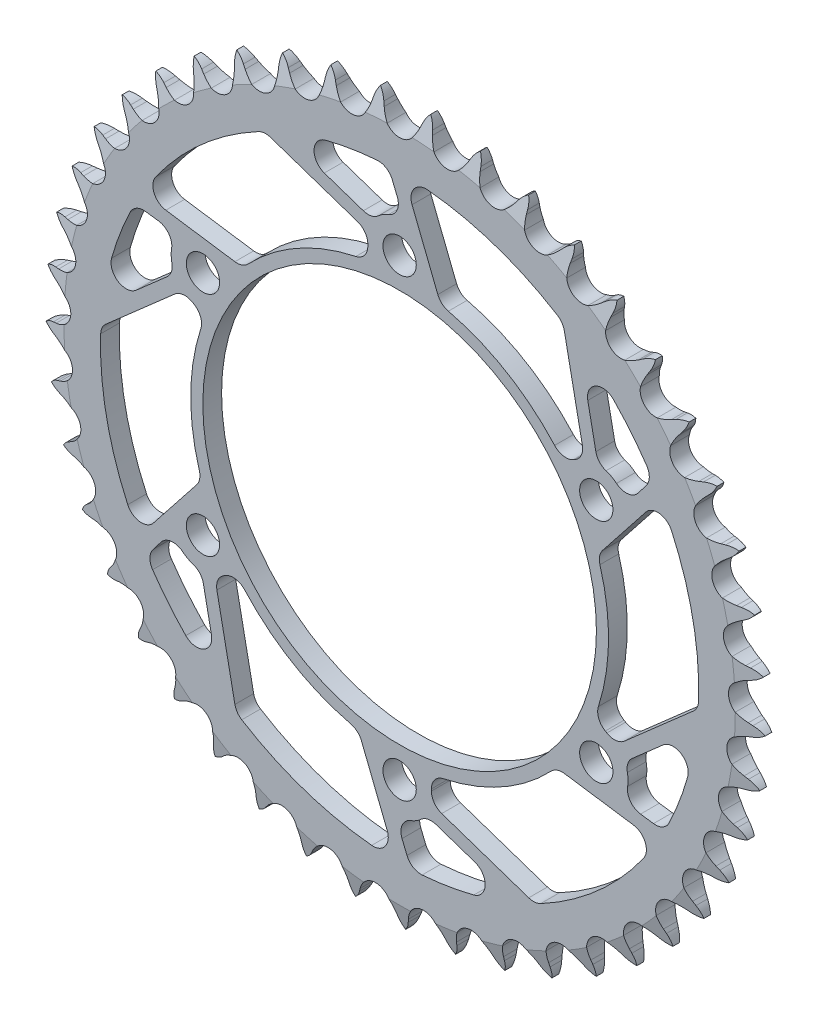
SolidWorks part; units mm, degrees
material "7075-T6, Plate (SS)"
ref_plane "Front Plane" through (0, 0, 0) normal (0, 0, 1) x (1, 0, 0)
ref_plane "Top Plane" through (0, 0, 0) normal (0, 1, 0) x (1, 0, 0)
ref_plane "Right Plane" through (0, 0, 0) normal (1, 0, 0) x (0, 0, -1)
sketch "Sketch2" plane through (0, 0, 0) normal (0, 0, 1) x (1, 0, 0)
  line L0 (0, 0) -> (0, 206.7692) construction
  line L1 (5.9565, 114.1573) -> (6.3871, 115.3681)
  line L2 (9.9891, 113.8753) -> (9.7312, 115.1342)
  line L3 (21.7861, 112.2174) -> (22.381, 113.3564)
  line L4 (25.7403, 111.3769) -> (25.6601, 112.6594)
  line L5 (37.1917, 108.0932) -> (37.9394, 109.1384)
  line L6 (-5.9565, 114.1573) -> (-6.3871, 115.3681)
  line L7 (40.9905, 106.7106) -> (41.0896, 107.9918)
  line L8 (51.8735, 101.8652) -> (52.7593, 102.7961)
  line L9 (55.4428, 99.9673) -> (55.7192, 101.2223)
  line L10 (65.5455, 93.6545) -> (66.5523, 94.4531)
  line L11 (68.816, 91.2783) -> (69.2644, 92.4826)
  line L12 (77.9418, 83.6208) -> (79.0499, 84.2716)
  line L13 (-15.8363, 112.6813) -> (-11.3291, 110.2511) construction
  line L14 (-8.2868, 118.5072) -> (3479.5369, -49759.6953) construction
  line L15 (80.8498, 80.8127) -> (81.4614, 81.9428)
  line L16 (88.8211, 71.9597) -> (90.009, 72.4498)
  line L17 (91.3099, 68.7741) -> (92.0729, 69.8081)
  line L18 (97.9715, 58.8978) -> (99.2161, 59.2179)
  line L19 (99.9928, 55.3969) -> (100.8922, 56.3147)
  line L20 (105.2151, 44.6897) -> (106.492, 44.8334)
  line L21 (106.7294, 40.9415) -> (107.7479, 41.7251)
  line L22 (110.4107, 29.6116) -> (111.6953, 29.5762)
  line L23 (111.3887, 25.6892) -> (112.5063, 26.3235)
  line L24 (113.4573, 13.9573) -> (114.7245, 13.7434)
  line L25 (113.8799, 9.9369) -> (115.0749, 10.4095)
  line L26 (114.2957, -1.9688) -> (115.5207, -2.3569)
  line L27 (114.1546, -6.0089) -> (115.4037, -5.7072)
  line L28 (112.9093, -17.8565) -> (114.0685, -18.4113)
  line L29 (112.2074, -21.8376) -> (113.4863, -21.7127)
  line L30 (109.3254, -33.3967) -> (110.396, -34.1074)
  line L31 (108.0761, -37.2414) -> (109.3601, -37.2957)
  line L32 (103.6135, -48.2868) -> (104.5748, -49.1396)
  line L33 (101.8414, -51.9202) -> (103.1052, -52.1527)
  line L34 (95.8849, -62.2371) -> (96.7182, -63.2154)
  line L35 (93.6244, -65.5885) -> (94.8436, -65.9946)
  line L36 (86.29, -74.976) -> (86.979, -76.0608)
  line L37 (83.585, -77.9802) -> (84.7359, -78.552)
  line L38 (75.0156, -86.2556) -> (75.5469, -87.4257)
  line L39 (71.9189, -88.8541) -> (72.9789, -89.5805)
  line L40 (62.2811, -95.8563) -> (62.6444, -97.089)
  line L41 (58.8528, -97.9985) -> (59.8015, -98.8654)
  line L42 (48.3344, -103.5913) -> (48.5226, -104.8625)
  line L43 (44.6413, -105.2356) -> (45.4601, -106.226)
  line L44 (33.4469, -109.31) -> (33.4563, -110.595)
  line L45 (29.5609, -110.4243) -> (30.2339, -111.5191)
  line L46 (17.9084, -112.9011) -> (17.7389, -114.175)
  line L47 (13.9052, -113.4637) -> (14.4192, -114.6415)
  line L48 (2.0213, -114.2947) -> (1.6762, -115.5326)
  line L49 (-2.0213, -114.2947) -> (-1.6762, -115.5326)
  line L50 (-13.9052, -113.4637) -> (-14.4192, -114.6415)
  line L51 (-17.9084, -112.9011) -> (-17.7389, -114.175)
  line L52 (-29.5609, -110.4243) -> (-30.2339, -111.5191)
  line L53 (-33.4469, -109.31) -> (-33.4563, -110.595)
  line L54 (-44.6413, -105.2356) -> (-45.4601, -106.226)
  line L55 (-48.3344, -103.5913) -> (-48.5226, -104.8625)
  line L56 (-58.8528, -97.9985) -> (-59.8015, -98.8654)
  line L57 (-62.2811, -95.8563) -> (-62.6444, -97.089)
  line L58 (-71.9189, -88.8541) -> (-72.9789, -89.5805)
  line L59 (-75.0156, -86.2556) -> (-75.5469, -87.4257)
  line L60 (-83.585, -77.9802) -> (-84.7359, -78.552)
  line L61 (-86.29, -74.976) -> (-86.979, -76.0608)
  line L62 (-93.6244, -65.5885) -> (-94.8436, -65.9946)
  line L63 (-95.8849, -62.2371) -> (-96.7182, -63.2154)
  line L64 (-101.8414, -51.9202) -> (-103.1052, -52.1527)
  line L65 (-103.6135, -48.2868) -> (-104.5748, -49.1396)
  line L66 (-108.0761, -37.2414) -> (-109.3601, -37.2957)
  line L67 (-109.3254, -33.3967) -> (-110.396, -34.1074)
  line L68 (-112.2074, -21.8376) -> (-113.4863, -21.7127)
  line L69 (-112.9093, -17.8565) -> (-114.0685, -18.4113)
  line L70 (-114.1546, -6.0089) -> (-115.4037, -5.7072)
  line L71 (-114.2957, -1.9688) -> (-115.5207, -2.3569)
  line L72 (-113.8799, 9.9369) -> (-115.0749, 10.4095)
  line L73 (-113.4573, 13.9573) -> (-114.7245, 13.7434)
  line L74 (-111.3887, 25.6892) -> (-112.5063, 26.3235)
  line L75 (-110.4107, 29.6116) -> (-111.6953, 29.5762)
  line L76 (-106.7294, 40.9415) -> (-107.7479, 41.7251)
  line L77 (-105.2151, 44.6897) -> (-106.492, 44.8334)
  line L78 (-99.9928, 55.3969) -> (-100.8922, 56.3147)
  line L79 (-97.9715, 58.8978) -> (-99.2161, 59.2179)
  line L80 (-91.3099, 68.7741) -> (-92.0729, 69.8081)
  line L81 (-88.8211, 71.9597) -> (-90.009, 72.4498)
  line L82 (-80.8498, 80.8127) -> (-81.4614, 81.9428)
  line L83 (-77.9418, 83.6208) -> (-79.0499, 84.2716)
  line L84 (-68.816, 91.2783) -> (-69.2644, 92.4826)
  line L85 (-65.5455, 93.6545) -> (-66.5523, 94.4531)
  line L86 (-55.4428, 99.9673) -> (-55.7192, 101.2223)
  line L87 (-51.8735, 101.8652) -> (-52.7593, 102.7961)
  line L88 (-40.9905, 106.7106) -> (-41.0896, 107.9918)
  line L89 (-37.1917, 108.0932) -> (-37.9394, 109.1384)
  line L90 (-25.7403, 111.3769) -> (-25.6601, 112.6594)
  line L91 (-21.7861, 112.2174) -> (-22.381, 113.3564)
  line L92 (-9.9891, 113.8753) -> (-9.7312, 115.1342)
  line L93 (-13.6479, 112.8344) -> (49864.5546, 3600.6581) construction
  line L94 (0, 113.7887) -> (48259.6069, -12963.3036) construction
  circle A0 centre (0, 0) radius 113.7887 construction
  arc A2 (-4.1251, 110.7548) -> (-5.9565, 114.1573) centre (6.521, 118.6791) cw
  arc A4 (-4.1251, 110.7548) -> (4.1251, 110.7548) centre (0, 113.7887) ccw
  arc A5 (-6.3871, 115.3681) -> (-8.2868, 118.5072) centre (-14.1858, 112.7928) ccw
  arc A6 (6.3871, 115.3681) -> (8.2868, 118.5072) centre (14.1858, 112.7928) cw
  arc A7 (4.1251, 110.7548) -> (5.9565, 114.1573) centre (-6.521, 118.6791) ccw
  arc A8 (9.7312, 115.1342) -> (8.2868, 118.5072) centre (1.65, 113.6694) ccw
  arc A9 (11.3291, 110.2511) -> (9.9891, 113.8753) centre (22.9745, 116.6165) cw
  arc A10 (11.3291, 110.2511) -> (19.4991, 109.1029) centre (15.8363, 112.6813) ccw
  arc A11 (19.4991, 109.1029) -> (21.7861, 112.2174) centre (10.0594, 118.4316) ccw
  arc A12 (22.381, 113.3564) -> (24.6992, 116.2006) centre (29.7455, 109.7208) cw
  arc A13 (25.6601, 112.6594) -> (24.6992, 116.2006) centre (17.4537, 112.3336) ccw
  arc A14 (26.5629, 107.6014) -> (25.7403, 111.3769) centre (38.9808, 112.2842) cw
  arc A15 (26.5629, 107.6014) -> (34.4935, 105.3273) centre (31.3644, 109.3807) ccw
  arc A16 (34.4935, 105.3273) -> (37.1917, 108.0932) centre (26.444, 115.8791) ccw
  arc A17 (37.9394, 109.1384) -> (40.6308, 111.6323) centre (44.7262, 104.5133) cw
  arc A18 (41.0896, 107.9918) -> (40.6308, 111.6323) centre (32.9176, 108.8112) ccw
  arc A19 (41.2796, 102.8574) -> (40.9905, 106.7106) centre (54.2283, 105.7664) cw
  arc A20 (41.2796, 102.8574) -> (48.8165, 99.5017) centre (46.282, 103.9512) ccw
  arc A21 (48.8165, 99.5017) -> (51.8735, 101.8652) centre (42.3139, 111.071) ccw
  arc A22 (52.7593, 102.7961) -> (55.7716, 104.8912) centre (58.8363, 97.2715) cw
  arc A23 (55.7192, 101.2223) -> (55.7716, 104.8912) centre (47.7409, 103.1711) ccw
  arc A24 (55.1928, 96.1114) -> (55.4428, 99.9673) centre (68.4204, 97.19) cw
  arc A25 (55.1928, 96.1114) -> (62.1894, 91.7395) centre (60.2988, 96.4983) ccw
  arc A26 (62.1894, 91.7395) -> (65.5455, 93.6545) centre (57.3602, 104.1012) ccw
  arc A27 (66.5523, 94.4531) -> (69.8269, 96.1085) centre (71.8013, 88.1364) cw
  arc A28 (69.2644, 92.4826) -> (69.8269, 96.1085) centre (61.6349, 95.5228) ccw
  arc A29 (68.0318, 87.4947) -> (68.816, 91.2783) centre (81.2808, 86.7218) cw
  arc A30 (68.0318, 87.4947) -> (74.3518, 82.1916) centre (73.142, 87.1672) ccw
  arc A31 (74.3518, 82.1916) -> (77.9418, 83.6208) centre (71.2901, 95.105) ccw
  arc A32 (79.0499, 84.2716) -> (82.5231, 85.4551) centre (83.3688, 77.2859) cw
  arc A33 (81.4614, 81.9428) -> (82.5231, 85.4551) centre (74.3293, 86.0152) ccw
  arc A34 (79.5466, 77.175) -> (80.8498, 80.8127) centre (92.5591, 74.5658) cw
  arc A35 (79.5466, 77.175) -> (85.0671, 71.0439) centre (84.5615, 76.1395) ccw
  arc A36 (85.0671, 71.0439) -> (88.8211, 71.9597) centre (83.8323, 84.2578) ccw
  arc A37 (90.009, 72.4498) -> (93.613, 73.1385) centre (93.3135, 64.931) cw
  arc A38 (92.0729, 69.8081) -> (93.613, 73.1385) centre (85.5769, 74.8335) ccw
  arc A39 (89.5132, 65.3532) -> (91.3099, 68.7741) centre (102.0359, 60.9583) cw
  arc A40 (89.5132, 65.3532) -> (94.1266, 58.5135) centre (94.3351, 63.6298) ccw
  arc A41 (94.1266, 58.5135) -> (97.9715, 58.8978) centre (94.7429, 71.7706) ccw
  arc A42 (99.2161, 59.2179) -> (102.8809, 59.3983) centre (101.4421, 51.3124) cw
  arc A43 (100.8922, 56.3147) -> (102.8809, 59.3983) centre (95.1589, 62.1952) ccw
  arc A44 (97.7375, 52.2593) -> (99.9928, 55.3969) centre (109.5266, 46.1645) cw
  arc A45 (97.7375, 52.2593) -> (101.3541, 44.8441) centre (102.2726, 49.8817) ccw
  arc A46 (101.3541, 44.8441) -> (105.2151, 44.6897) centre (103.8094, 57.8865) ccw
  arc A47 (106.492, 44.8334) -> (110.1463, 44.502) centre (107.5962, 36.695) cw
  arc A48 (107.7479, 41.7251) -> (110.1463, 44.502) centre (102.8887, 48.3464) ccw
  arc A49 (104.0594, 38.1483) -> (106.7294, 40.9415) centre (114.8856, 30.472) cw
  arc A50 (104.0594, 38.1483) -> (106.6088, 30.3019) centre (108.2195, 35.1626) ccw
  arc A51 (106.6088, 30.3019) -> (110.4107, 29.6116) centre (110.8554, 42.8757) ccw
  arc A52 (111.6953, 29.5762) -> (115.2678, 28.7395) centre (111.656, 21.3634) cw
  arc A53 (112.5063, 26.3235) -> (115.2678, 28.7395) centre (108.6159, 33.5565) ccw
  arc A54 (108.3559, 23.2948) -> (111.3887, 25.6892) centre (118.0084, 14.1865) cw
  arc A55 (108.3559, 23.2948) -> (109.7885, 15.1699) centre (112.06, 19.7592) ccw
  arc A56 (109.7885, 15.1699) -> (113.4573, 13.9573) centre (115.7437, 27.0303) ccw
  arc A57 (114.7245, 13.7434) -> (118.1458, 12.4176) centre (113.5426, 5.616) cw
  arc A58 (115.0749, 10.4095) -> (118.1458, 12.4176) centre (112.229, 18.1136) ccw
  arc A59 (110.5434, 7.9879) -> (113.8799, 9.9369) centre (118.8343, -2.3752) cw
  arc A60 (110.5434, 7.9879) -> (110.8313, -0.2573) centre (113.7194, 3.9712) ccw
  arc A61 (110.8313, -0.2573) -> (114.2957, -1.9688) centre (118.3792, 10.6589) ccw
  arc A62 (115.5207, -2.3569) -> (118.7242, -4.1459) centre (113.2192, -10.2407) cw
  arc A63 (115.4037, -5.7072) -> (118.7242, -4.1459) centre (113.6577, 2.318) ccw
  arc A64 (110.5793, -7.4745) -> (114.1546, -6.0089) centre (117.3473, -18.8906) cw
  arc A65 (110.5793, -7.4745) -> (109.7169, -15.6795) centre (113.1654, -11.8942) ccw
  arc A66 (109.7169, -15.6795) -> (112.9093, -17.8565) centre (118.7106, -5.9201) ccw
  arc A67 (114.0685, -18.4113) -> (116.9918, -20.6288) centre (110.6921, -25.8981) cw
  arc A68 (113.4863, -21.7127) -> (116.9918, -20.6288) centre (112.8742, -13.5226) ccw
  arc A69 (108.4629, -22.7914) -> (112.2074, -21.8376) centre (113.5762, -35.0384) cw
  arc A70 (108.4629, -22.7914) -> (106.467, -30.7966) centre (110.4087, -27.528) ccw
  arc A71 (106.467, -30.7966) -> (109.3254, -33.3967) centre (116.7314, -22.3838) ccw
  arc A72 (110.396, -34.1074) -> (112.9823, -36.7102) centre (106.0105, -41.0515) cw
  arc A73 (109.3601, -37.2957) -> (112.9823, -36.7102) centre (109.8938, -29.1001) ccw
  arc A74 (104.2354, -37.6648) -> (108.0761, -37.2414) centre (107.5945, -50.5041) cw
  arc A75 (104.2354, -37.6648) -> (101.1448, -45.3142) centre (105.5031, -42.626) ccw
  arc A76 (101.1448, -45.3142) -> (103.6135, -48.2868) centre (112.4801, -38.4118) ccw
  arc A77 (104.5748, -49.1396) -> (106.7737, -52.077) centre (99.2656, -55.4058) cw
  arc A78 (103.1052, -52.1527) -> (106.7737, -52.077) centre (104.7743, -44.1112) ccw
  arc A79 (97.979, -51.805) -> (101.8414, -51.9202) centre (99.5186, -64.9869) cw
  arc A80 (97.979, -51.805) -> (93.8539, -58.9499) centre (98.5439, -56.8944) ccw
  arc A81 (93.8539, -58.9499) -> (95.8849, -62.2371) centre (106.0396, -53.6922) ccw
  arc A82 (96.7182, -63.2154) -> (98.4869, -66.4302) centre (90.5886, -68.6817) cw
  arc A83 (94.8436, -65.9946) -> (98.4869, -66.4302) centre (97.6156, -58.2636) ccw
  arc A84 (89.8157, -64.9369) -> (93.6244, -65.5885) centre (89.5057, -78.2047) cw
  arc A85 (89.8157, -64.9369) -> (84.7363, -71.4381) centre (89.6667, -70.0553) ccw
  arc A86 (84.7363, -71.4381) -> (86.29, -74.976) centre (97.5351, -67.9275) ccw
  arc A87 (86.979, -76.0608) -> (88.2831, -79.4905) centre (80.1483, -80.6207) cw
  arc A88 (84.7359, -78.552) -> (88.2831, -79.4905) centre (88.5569, -71.2821) ccw
  arc A89 (79.9041, -76.8048) -> (83.585, -77.9802) centre (77.7506, -89.9004) cw
  arc A90 (79.9041, -76.8048) -> (73.9694, -82.5359) centre (79.0443, -81.8528) ccw
  arc A91 (73.9694, -82.5359) -> (75.0156, -86.2556) centre (87.1322, -80.8407) ccw
  arc A92 (75.5469, -87.4257) -> (76.361, -91.0035) centre (68.1481, -90.9906) cw
  arc A93 (72.9789, -89.5805) -> (76.361, -91.0035) centre (77.7745, -82.9131) ccw
  arc A94 (68.4373, -87.1779) -> (71.9189, -88.8541) centre (64.4822, -99.8463) cw
  arc A95 (68.4373, -87.1779) -> (61.7628, -92.0272) centre (66.8833, -92.057) ccw
  arc A96 (61.7628, -92.0272) -> (62.2811, -95.8563) centre (75.0334, -92.1804) ccw
  arc A97 (62.6444, -97.089) -> (62.9526, -100.7452) centre (54.8214, -99.5895) cw
  arc A98 (59.8015, -98.8654) -> (62.9526, -100.7452) centre (65.4783, -92.9303) ccw
  arc A99 (55.6385, -95.8541) -> (58.8528, -97.9985) centre (49.9588, -107.8488) cw
  arc A100 (55.6385, -95.8541) -> (48.354, -99.7273) centre (53.4206, -100.4695) ccw
  arc A101 (48.354, -99.7273) -> (48.3344, -103.5913) centre (61.4741, -101.726) ccw
  arc A102 (48.5226, -104.8625) -> (48.3189, -108.5261) centre (40.4277, -106.25) cw
  arc A103 (45.4601, -106.226) -> (48.3189, -108.5261) centre (51.9077, -101.1388) ccw
  arc A104 (41.7567, -102.6646) -> (44.6413, -105.2356) centre (34.4629, -113.7522) cw
  arc A105 (41.7567, -102.6646) -> (34.0041, -105.4864) centre (38.918, -106.9264) ccw
  arc A106 (34.0041, -105.4864) -> (33.4469, -109.31) centre (46.7184, -109.2915) ccw
  arc A107 (33.4563, -110.595) -> (32.7448, -114.1946) centre (25.2471, -110.8424) cw
  arc A108 (30.2339, -111.5191) -> (32.7448, -114.1946) centre (37.3267, -107.3786) ccw
  arc A109 (27.0622, -107.4769) -> (29.5609, -110.4243) centre (18.2963, -117.4414) cw
  arc A110 (27.0622, -107.4769) -> (18.9923, -109.1922) centre (23.658, -111.3022) ccw
  arc A111 (18.9923, -109.1922) -> (17.9084, -112.9011) centre (31.0533, -114.7299) ccw
  arc A112 (17.7389, -114.175) -> (16.5333, -117.6405) centre (9.5752, -113.2774) cw
  arc A113 (14.4192, -114.6415) -> (16.5333, -117.6405) centre (22.0193, -111.5285) ccw
  arc A114 (11.8409, -110.1973) -> (13.9052, -113.4637) centre (1.7735, -118.8448) cw
  arc A115 (11.8409, -110.1973) -> (3.6108, -110.7728) centre (7.9375, -113.5115) ccw
  arc A116 (3.6108, -110.7728) -> (2.0213, -114.2947) centre (14.7837, -117.9351) ccw
  arc A117 (1.6762, -115.5326) -> (0, -118.7966) centre (-6.2832, -113.5076) cw
  arc A118 (-1.6762, -115.5326) -> (0, -118.7966) centre (6.2832, -113.5076) ccw
  arc A119 (-3.6108, -110.7728) -> (-2.0213, -114.2947) centre (-14.7837, -117.9351) cw
  arc A120 (-3.6108, -110.7728) -> (-11.8409, -110.1973) centre (-7.9375, -113.5115) ccw
  arc A121 (-11.8409, -110.1973) -> (-13.9052, -113.4637) centre (-1.7735, -118.8448) ccw
  arc A122 (-14.4192, -114.6415) -> (-16.5333, -117.6405) centre (-22.0193, -111.5285) cw
  arc A123 (-17.7389, -114.175) -> (-16.5333, -117.6405) centre (-9.5752, -113.2774) ccw
  arc A124 (-18.9923, -109.1922) -> (-17.9084, -112.9011) centre (-31.0533, -114.7299) cw
  arc A125 (-18.9923, -109.1922) -> (-27.0622, -107.4769) centre (-23.658, -111.3022) ccw
  arc A126 (-27.0622, -107.4769) -> (-29.5609, -110.4243) centre (-18.2963, -117.4414) ccw
  arc A127 (-30.2339, -111.5191) -> (-32.7448, -114.1946) centre (-37.3267, -107.3786) cw
  arc A128 (-33.4563, -110.595) -> (-32.7448, -114.1946) centre (-25.2471, -110.8424) ccw
  arc A129 (-34.0041, -105.4864) -> (-33.4469, -109.31) centre (-46.7184, -109.2915) cw
  arc A130 (-34.0041, -105.4864) -> (-41.7567, -102.6646) centre (-38.918, -106.9264) ccw
  arc A131 (-41.7567, -102.6646) -> (-44.6413, -105.2356) centre (-34.4629, -113.7522) ccw
  arc A132 (-45.4601, -106.226) -> (-48.3189, -108.5261) centre (-51.9077, -101.1388) cw
  arc A133 (-48.5226, -104.8625) -> (-48.3189, -108.5261) centre (-40.4277, -106.25) ccw
  arc A134 (-48.354, -99.7273) -> (-48.3344, -103.5913) centre (-61.4741, -101.726) cw
  arc A135 (-48.354, -99.7273) -> (-55.6385, -95.8541) centre (-53.4206, -100.4695) ccw
  arc A136 (-55.6385, -95.8541) -> (-58.8528, -97.9985) centre (-49.9588, -107.8488) ccw
  arc A137 (-59.8015, -98.8654) -> (-62.9526, -100.7452) centre (-65.4783, -92.9303) cw
  arc A138 (-62.6444, -97.089) -> (-62.9526, -100.7452) centre (-54.8214, -99.5895) ccw
  arc A139 (-61.7628, -92.0272) -> (-62.2811, -95.8563) centre (-75.0334, -92.1804) cw
  arc A140 (-61.7628, -92.0272) -> (-68.4373, -87.1779) centre (-66.8833, -92.057) ccw
  arc A141 (-68.4373, -87.1779) -> (-71.9189, -88.8541) centre (-64.4822, -99.8463) ccw
  arc A142 (-72.9789, -89.5805) -> (-76.361, -91.0035) centre (-77.7745, -82.9131) cw
  arc A143 (-75.5469, -87.4257) -> (-76.361, -91.0035) centre (-68.1481, -90.9906) ccw
  arc A144 (-73.9694, -82.5359) -> (-75.0156, -86.2556) centre (-87.1322, -80.8407) cw
  arc A145 (-73.9694, -82.5359) -> (-79.9041, -76.8048) centre (-79.0443, -81.8528) ccw
  arc A146 (-79.9041, -76.8048) -> (-83.585, -77.9802) centre (-77.7506, -89.9004) ccw
  arc A147 (-84.7359, -78.552) -> (-88.2831, -79.4905) centre (-88.5569, -71.2821) cw
  arc A148 (-86.979, -76.0608) -> (-88.2831, -79.4905) centre (-80.1483, -80.6207) ccw
  arc A149 (-84.7363, -71.4381) -> (-86.29, -74.976) centre (-97.5351, -67.9275) cw
  arc A150 (-84.7363, -71.4381) -> (-89.8157, -64.9369) centre (-89.6667, -70.0553) ccw
  arc A151 (-89.8157, -64.9369) -> (-93.6244, -65.5885) centre (-89.5057, -78.2047) ccw
  arc A152 (-94.8436, -65.9946) -> (-98.4869, -66.4302) centre (-97.6156, -58.2636) cw
  arc A153 (-96.7182, -63.2154) -> (-98.4869, -66.4302) centre (-90.5886, -68.6817) ccw
  arc A154 (-93.8539, -58.9499) -> (-95.8849, -62.2371) centre (-106.0396, -53.6922) cw
  arc A155 (-93.8539, -58.9499) -> (-97.979, -51.805) centre (-98.5439, -56.8944) ccw
  arc A156 (-97.979, -51.805) -> (-101.8414, -51.9202) centre (-99.5186, -64.9869) ccw
  arc A157 (-103.1052, -52.1527) -> (-106.7737, -52.077) centre (-104.7743, -44.1112) cw
  arc A158 (-104.5748, -49.1396) -> (-106.7737, -52.077) centre (-99.2656, -55.4058) ccw
  arc A159 (-101.1448, -45.3142) -> (-103.6135, -48.2868) centre (-112.4801, -38.4118) cw
  arc A160 (-101.1448, -45.3142) -> (-104.2354, -37.6648) centre (-105.5031, -42.626) ccw
  arc A161 (-104.2354, -37.6648) -> (-108.0761, -37.2414) centre (-107.5945, -50.5041) ccw
  arc A162 (-109.3601, -37.2957) -> (-112.9823, -36.7102) centre (-109.8938, -29.1001) cw
  arc A163 (-110.396, -34.1074) -> (-112.9823, -36.7102) centre (-106.0105, -41.0515) ccw
  arc A164 (-106.467, -30.7966) -> (-109.3254, -33.3967) centre (-116.7314, -22.3838) cw
  arc A165 (-106.467, -30.7966) -> (-108.4629, -22.7914) centre (-110.4087, -27.528) ccw
  arc A166 (-108.4629, -22.7914) -> (-112.2074, -21.8376) centre (-113.5762, -35.0384) ccw
  arc A167 (-113.4863, -21.7127) -> (-116.9918, -20.6288) centre (-112.8742, -13.5226) cw
  arc A168 (-114.0685, -18.4113) -> (-116.9918, -20.6288) centre (-110.6921, -25.8981) ccw
  arc A169 (-109.7169, -15.6795) -> (-112.9093, -17.8565) centre (-118.7106, -5.9201) cw
  arc A170 (-109.7169, -15.6795) -> (-110.5793, -7.4745) centre (-113.1654, -11.8942) ccw
  arc A171 (-110.5793, -7.4745) -> (-114.1546, -6.0089) centre (-117.3473, -18.8906) ccw
  arc A172 (-115.4037, -5.7072) -> (-118.7242, -4.1459) centre (-113.6577, 2.318) cw
  arc A173 (-115.5207, -2.3569) -> (-118.7242, -4.1459) centre (-113.2192, -10.2407) ccw
  arc A174 (-110.8313, -0.2573) -> (-114.2957, -1.9688) centre (-118.3792, 10.6589) cw
  arc A175 (-110.8313, -0.2573) -> (-110.5434, 7.9879) centre (-113.7194, 3.9712) ccw
  arc A176 (-110.5434, 7.9879) -> (-113.8799, 9.9369) centre (-118.8343, -2.3752) ccw
  arc A177 (-115.0749, 10.4095) -> (-118.1458, 12.4176) centre (-112.229, 18.1136) cw
  arc A178 (-114.7245, 13.7434) -> (-118.1458, 12.4176) centre (-113.5426, 5.616) ccw
  arc A179 (-109.7885, 15.1699) -> (-113.4573, 13.9573) centre (-115.7437, 27.0303) cw
  arc A180 (-109.7885, 15.1699) -> (-108.3559, 23.2948) centre (-112.06, 19.7592) ccw
  arc A181 (-108.3559, 23.2948) -> (-111.3887, 25.6892) centre (-118.0084, 14.1865) ccw
  arc A182 (-112.5063, 26.3235) -> (-115.2678, 28.7395) centre (-108.6159, 33.5565) cw
  arc A183 (-111.6953, 29.5762) -> (-115.2678, 28.7395) centre (-111.656, 21.3634) ccw
  arc A184 (-106.6088, 30.3019) -> (-110.4107, 29.6116) centre (-110.8554, 42.8757) cw
  arc A185 (-106.6088, 30.3019) -> (-104.0594, 38.1483) centre (-108.2195, 35.1626) ccw
  arc A186 (-104.0594, 38.1483) -> (-106.7294, 40.9415) centre (-114.8856, 30.472) ccw
  arc A187 (-107.7479, 41.7251) -> (-110.1463, 44.502) centre (-102.8887, 48.3464) cw
  arc A188 (-106.492, 44.8334) -> (-110.1463, 44.502) centre (-107.5962, 36.695) ccw
  arc A189 (-101.3541, 44.8441) -> (-105.2151, 44.6897) centre (-103.8094, 57.8865) cw
  arc A190 (-101.3541, 44.8441) -> (-97.7375, 52.2593) centre (-102.2726, 49.8817) ccw
  arc A191 (-97.7375, 52.2593) -> (-99.9928, 55.3969) centre (-109.5266, 46.1645) ccw
  arc A192 (-100.8922, 56.3147) -> (-102.8809, 59.3983) centre (-95.1589, 62.1952) cw
  arc A193 (-99.2161, 59.2179) -> (-102.8809, 59.3983) centre (-101.4421, 51.3124) ccw
  arc A194 (-94.1266, 58.5135) -> (-97.9715, 58.8978) centre (-94.7429, 71.7706) cw
  arc A195 (-94.1266, 58.5135) -> (-89.5132, 65.3532) centre (-94.3351, 63.6298) ccw
  arc A196 (-89.5132, 65.3532) -> (-91.3099, 68.7741) centre (-102.0359, 60.9583) ccw
  arc A197 (-92.0729, 69.8081) -> (-93.613, 73.1385) centre (-85.5769, 74.8335) cw
  arc A198 (-90.009, 72.4498) -> (-93.613, 73.1385) centre (-93.3135, 64.931) ccw
  arc A199 (-85.0671, 71.0439) -> (-88.8211, 71.9597) centre (-83.8323, 84.2578) cw
  arc A200 (-85.0671, 71.0439) -> (-79.5466, 77.175) centre (-84.5615, 76.1395) ccw
  arc A201 (-79.5466, 77.175) -> (-80.8498, 80.8127) centre (-92.5591, 74.5658) ccw
  arc A202 (-81.4614, 81.9428) -> (-82.5231, 85.4551) centre (-74.3293, 86.0152) cw
  arc A203 (-79.0499, 84.2716) -> (-82.5231, 85.4551) centre (-83.3688, 77.2859) ccw
  arc A204 (-74.3518, 82.1916) -> (-77.9418, 83.6208) centre (-71.2901, 95.105) cw
  arc A205 (-74.3518, 82.1916) -> (-68.0318, 87.4947) centre (-73.142, 87.1672) ccw
  arc A206 (-68.0318, 87.4947) -> (-68.816, 91.2783) centre (-81.2808, 86.7218) ccw
  arc A207 (-69.2644, 92.4826) -> (-69.8269, 96.1085) centre (-61.6349, 95.5228) cw
  arc A208 (-66.5523, 94.4531) -> (-69.8269, 96.1085) centre (-71.8013, 88.1364) ccw
  arc A209 (-62.1894, 91.7395) -> (-65.5455, 93.6545) centre (-57.3602, 104.1012) cw
  arc A210 (-62.1894, 91.7395) -> (-55.1928, 96.1114) centre (-60.2988, 96.4983) ccw
  arc A211 (-55.1928, 96.1114) -> (-55.4428, 99.9673) centre (-68.4204, 97.19) ccw
  arc A212 (-55.7192, 101.2223) -> (-55.7716, 104.8912) centre (-47.7409, 103.1711) cw
  arc A213 (-52.7593, 102.7961) -> (-55.7716, 104.8912) centre (-58.8363, 97.2715) ccw
  arc A214 (-48.8165, 99.5017) -> (-51.8735, 101.8652) centre (-42.3139, 111.071) cw
  arc A215 (-48.8165, 99.5017) -> (-41.2796, 102.8574) centre (-46.282, 103.9512) ccw
  arc A216 (-41.2796, 102.8574) -> (-40.9905, 106.7106) centre (-54.2283, 105.7664) ccw
  arc A217 (-41.0896, 107.9918) -> (-40.6308, 111.6323) centre (-32.9176, 108.8112) cw
  arc A218 (-37.9394, 109.1384) -> (-40.6308, 111.6323) centre (-44.7262, 104.5133) ccw
  arc A219 (-34.4935, 105.3273) -> (-37.1917, 108.0932) centre (-26.444, 115.8791) cw
  arc A220 (-34.4935, 105.3273) -> (-26.5629, 107.6014) centre (-31.3644, 109.3807) ccw
  arc A221 (-26.5629, 107.6014) -> (-25.7403, 111.3769) centre (-38.9808, 112.2842) ccw
  arc A222 (-25.6601, 112.6594) -> (-24.6992, 116.2006) centre (-17.4537, 112.3336) cw
  arc A223 (-22.381, 113.3564) -> (-24.6992, 116.2006) centre (-29.7455, 109.7208) ccw
  arc A224 (-19.4991, 109.1029) -> (-21.7861, 112.2174) centre (-10.0594, 118.4316) cw
  arc A225 (-19.4991, 109.1029) -> (-11.3291, 110.2511) centre (-15.8363, 112.6813) ccw
  arc A226 (-11.3291, 110.2511) -> (-9.9891, 113.8753) centre (-22.9745, 116.6165) ccw
  arc A227 (-9.7312, 115.1342) -> (-8.2868, 118.5072) centre (-1.65, 113.6694) cw
  point P5 (4.1251, 110.7548)
  point P7 (0, 113.7887)
  point P9 (6.5478, 118.6044)
  point P12 (0, 118.6044)
  point P15 (6.5478, 113.7887)
  point P19 (6.3871, 115.3681)
  point P20 (8.2868, 118.5072)
  point P24 (-14.1894, 113.7887)
  point P25 (-14.1858, 112.7928)
  point P27 (19.4991, 109.1029)
  point P29 (0, 112.7965)
  point P30 (-8.2868, 118.5072)
  point P35 (-6.3871, 115.3681)
  point P43 (8.2868, 118.5072)
  point P45 (9.7312, 115.1342)
  point P49 (34.4935, 105.3273)
  point P59 (24.6992, 116.2006)
  point P61 (25.6601, 112.6594)
  point P65 (48.8165, 99.5017)
  point P75 (40.6308, 111.6323)
  point P77 (41.0896, 107.9918)
  point P81 (62.1894, 91.7395)
  point P91 (55.7716, 104.8912)
  point P93 (55.7192, 101.2223)
  point P97 (74.3518, 82.1916)
  point P107 (69.8269, 96.1085)
  point P109 (69.2644, 92.4826)
  point P113 (85.0671, 71.0439)
  point P123 (82.5231, 85.4551)
  point P125 (81.4614, 81.9428)
  point P126 (5.1653, 112.3891)
  point P129 (94.1266, 58.5135)
  point P139 (93.613, 73.1385)
  point P141 (92.0729, 69.8081)
  point P145 (101.3541, 44.8441)
  point P155 (102.8809, 59.3983)
  point P157 (100.8922, 56.3147)
  point P161 (106.6088, 30.3019)
  point P171 (110.1463, 44.502)
  point P173 (107.7479, 41.7251)
  point P177 (109.7885, 15.1699)
  point P187 (115.2678, 28.7395)
  point P189 (112.5063, 26.3235)
  point P193 (110.8313, -0.2573)
  point P203 (118.1458, 12.4176)
  point P205 (115.0749, 10.4095)
  point P209 (109.7169, -15.6795)
  point P219 (118.7242, -4.1459)
  point P221 (115.4037, -5.7072)
  point P225 (106.467, -30.7966)
  point P235 (116.9918, -20.6288)
  point P237 (113.4863, -21.7127)
  point P241 (101.1448, -45.3142)
  point P251 (112.9823, -36.7102)
  point P253 (109.3601, -37.2957)
  point P257 (93.8539, -58.9499)
  point P267 (106.7737, -52.077)
  point P269 (103.1052, -52.1527)
  point P273 (84.7363, -71.4381)
  point P283 (98.4869, -66.4302)
  point P285 (94.8436, -65.9946)
  point P289 (73.9694, -82.5359)
  point P299 (88.2831, -79.4904)
  point P301 (84.7359, -78.552)
  point P305 (61.7628, -92.0272)
  point P315 (76.361, -91.0035)
  point P317 (72.9789, -89.5805)
  point P321 (48.354, -99.7273)
  point P331 (62.9526, -100.7452)
  point P333 (59.8015, -98.8654)
  point P337 (34.0041, -105.4864)
  point P347 (48.3189, -108.5261)
  point P349 (45.4601, -106.226)
  point P353 (18.9923, -109.1922)
  point P363 (32.7448, -114.1946)
  point P365 (30.2339, -111.5191)
  point P369 (3.6108, -110.7728)
  point P379 (16.5333, -117.6405)
  point P381 (14.4192, -114.6415)
  point P385 (-11.8409, -110.1973)
  point P395 (0, -118.7966)
  point P397 (-1.6762, -115.5326)
  point P401 (-27.0622, -107.4769)
  point P411 (-16.5333, -117.6405)
  point P413 (-17.7389, -114.175)
  point P417 (-41.7567, -102.6646)
  point P427 (-32.7448, -114.1946)
  point P429 (-33.4563, -110.595)
  point P433 (-55.6385, -95.8541)
  point P443 (-48.3189, -108.5261)
  point P445 (-48.5226, -104.8625)
  point P449 (-68.4373, -87.1779)
  point P459 (-62.9526, -100.7452)
  point P461 (-62.6444, -97.089)
  point P465 (-79.9041, -76.8048)
  point P475 (-76.361, -91.0035)
  point P477 (-75.5469, -87.4257)
  point P481 (-89.8157, -64.9369)
  point P491 (-88.2831, -79.4904)
  point P493 (-86.979, -76.0608)
  point P497 (-97.979, -51.805)
  point P507 (-98.4869, -66.4302)
  point P509 (-96.7182, -63.2154)
  point P513 (-104.2354, -37.6648)
  point P523 (-106.7737, -52.077)
  point P525 (-104.5748, -49.1396)
  point P529 (-108.4629, -22.7914)
  point P539 (-112.9823, -36.7102)
  point P541 (-110.396, -34.1074)
  point P545 (-110.5793, -7.4745)
  point P555 (-116.9918, -20.6288)
  point P557 (-114.0685, -18.4113)
  point P561 (-110.5434, 7.9879)
  point P571 (-118.7242, -4.1459)
  point P573 (-115.5207, -2.3569)
  point P577 (-108.3559, 23.2948)
  point P587 (-118.1458, 12.4176)
  point P589 (-114.7245, 13.7434)
  point P593 (-104.0594, 38.1483)
  point P603 (-115.2678, 28.7395)
  point P605 (-111.6953, 29.5762)
  point P609 (-97.7375, 52.2593)
  point P619 (-110.1463, 44.502)
  point P621 (-106.492, 44.8334)
  point P625 (-89.5132, 65.3532)
  point P635 (-102.8809, 59.3983)
  point P637 (-99.2161, 59.2179)
  point P641 (-79.5466, 77.175)
  point P651 (-93.613, 73.1385)
  point P653 (-90.009, 72.4498)
  point P657 (-68.0318, 87.4947)
  point P667 (-82.5231, 85.4551)
  point P669 (-79.0499, 84.2716)
  point P673 (-55.1928, 96.1114)
  point P683 (-69.8269, 96.1085)
  point P685 (-66.5523, 94.4531)
  point P689 (-41.2796, 102.8574)
  point P699 (-55.7716, 104.8912)
  point P701 (-52.7593, 102.7961)
  point P705 (-26.5629, 107.6014)
  point P715 (-40.6308, 111.6323)
  point P717 (-37.9394, 109.1384)
  point P721 (-11.3291, 110.2511)
  point P731 (-24.6992, 116.2006)
  point P733 (-22.381, 113.3564)
  point P736 (0, 0)
  dimension "D1" = 227.5774
  dimension "D11" = 13.2715
  dimension "D2" = 45
extrude "Boss-Extrude2" add sketch "Sketch2" along normal blind 6.1976
ref_axis "Axis1" through (0, 0, -0.3099) along (0, 0, 1)
ref_plane "Plane1" through (0, 0, 3.0988) normal (0, 0, -1) x (-1, 0, 0)
ref_plane "Plane2" through (0, 0, 0) normal (-0.9781, -0.2079, 0) x (0, 0, 1)
sketch "Sketch4" plane through (0, 0, 0) normal (0.9781, 0.2079, 0) x (0, 0, -1)
  line L0 (-6.1976, 110.8591) -> (-4.2132, 118.7966)
  line L1 (-6.1976, 118.7966) -> (0, 118.7966) construction
  line L2 (-4.2132, 118.7966) -> (-6.1976, 118.7966)
  line L3 (-6.1976, 118.7966) -> (-6.1976, 110.8591)
  line L7 (-6.1976, 114.1946) -> (-6.1976, 110.595) construction
  line L8 (-6.1976, 100.7452) -> (-6.1976, 97.089) construction
  line L10 (-3.0988, -121.9024) -> (-3.0988, 121.9024) construction
  line L11 (0, 118.7966) -> (0, 110.8591)
  line L12 (-1.9844, 118.7966) -> (0, 118.7966)
  line L13 (0, 110.8591) -> (-1.9844, 118.7966)
  dimension "D1" = 7.9375
  dimension "D2" = 1.9844
revolve "Cut-Revolve1" cut sketch "Sketch4" angle 360 about axis through (0, 0, -0.3099) along (0, 0, 1) region at (-24.1491, 113.6126, 5.5361) region at (-24.1491, 113.6126, 0.6615)
hole_wizard "M10 Clearance Hole1" positions "Sketch6" profile "Sketch7" hole size "M10" standard "ANSI Metric" end condition through all
sketch "Sketch6" plane through (0, 0, 6.1976) normal (0, 0, 1) x (1, 0, 0)
  point P0 (0, 75)
  point P9 (64.9519, 37.5)
  point P10 (64.9519, -37.5)
  point P11 (0, -75)
  point P12 (-64.9519, -37.5)
  point P13 (-64.9519, 37.5)
  dimension "D1" = 75
  dimension "D2" = 6
sketch "Sketch7" plane through (0, 75, 6.1976) normal (1, 0, 0) x (0, -1, 0)
  line L0 (0, 0) -> (0, 6.1976)
  line L1 (0, 6.1976) -> (5.5, 6.1976)
  line L2 (5.5, 6.1976) -> (5.5, 0)
  line L5 (5.5, 0) -> (0, 0)
  line L11 (0, -6.35) -> (0, 107.95) construction
  dimension "Thru Hole Dia." = 11
  dimension "Thru Hole Depth" = 6.1976
sketch "Sketch5" plane through (0, 0, 6.1976) normal (0, 0, 1) x (1, 0, 0)
  circle A0 centre (0, 0) radius 65
  dimension "D1" = 130
extrude "Cut-Extrude1" cut sketch "Sketch5" against normal through all
sketch "Sketch8" plane through (0, 0, 6.1976) normal (0, 0, 1) x (1, 0, 0)
  line L0 (0, 0) -> (6958.655, 49513.4034) construction
  line L1 (0, 0) -> (0, 50000) construction
  line L2 (15.8363, 112.6813) -> (0, 113.7887) construction
  arc A0 (11.3291, 110.2511) -> (19.4991, 109.1029) centre (15.8363, 112.6813) ccw construction
  arc A1 (-4.1251, 110.7548) -> (4.1251, 110.7548) centre (0, 113.7887) ccw construction
  circle A2 centre (0, 113.7887) radius 5.08 construction
  point P6 (15.1237, 107.6105)
  point P12 (0, 108.6681)
  dimension "D1" = 10.16
sketch "Sketch9" plane through (0, 0, 6.1976) normal (0, 0, 1) x (1, 0, 0)
  line L0 (27.2, 63.4126) -> (-37.7731, 91.282) construction
  line L2 (0, 0) -> (72.5197, 125.6078) construction
  line L3 (0, -200000) -> (0, 250000) construction
  line L5 (-10.5, 64.1463) -> (-10.5, 75)
  line L6 (10.5, 75) -> (10.5, 64.1463)
  line L13 (0, 0) -> (-25000, 43301.2702) construction
  line L18 (-8.1504, 68.5169) -> (-78.3535, 60.1659) construction
  line L19 (-84.9388, 50.4441) -> (-51.7822, 45.6027)
  line L20 (-44.6581, 88.1185) -> (-10.3891, 76.5219)
  line L22 (1.278, 103.7809) -> (15.7757, 68.462)
  line L42 (-8.823, 80.6925) -> (-38.8178, 90.8427)
  line L43 (5.088, 77.0885) -> (-3.7896, 98.716)
  line L52 (-64.2166, 42.9506) -> (-87.3854, 46.0761)
  line L53 (-74.2932, 32.7053) -> (-98.081, 11.8042) [skipped]
  line L54 (-41.3169, 55.2622) -> (-97.9391, 12.9285) construction
  line L55 (74.2932, -32.7053) -> (98.081, -11.8042) [skipped]
  line L56 (64.2166, -42.9506) -> (87.3854, -46.0761) [skipped]
  line L57 (8.823, -80.6925) -> (38.8178, -90.8427) [skipped]
  line L58 (-5.088, -77.0885) -> (3.7896, -98.716) [skipped]
  line L59 (-65.4702, -47.9872) -> (-59.2632, -79.0385) [skipped]
  line L60 (-69.3046, -34.1379) -> (-83.5958, -52.6399) [skipped]
  line L61 (41.3169, -55.2622) -> (97.9391, -12.9285) construction
  line L62 (8.1504, -68.5169) -> (78.3535, -60.1659) construction
  line L63 (-27.2, -63.4126) -> (37.7731, -91.282) construction
  line L64 (-55.2622, -41.3169) -> (-12.9285, -97.9391) construction
  line L65 (-68.5169, -8.1504) -> (-60.1659, -78.3535) construction
  line L66 (-63.4126, 27.2) -> (-91.282, -37.7731) construction
  line L67 (63.4126, -27.2) -> (91.282, 37.7731) construction
  line L68 (65.4702, 47.9872) -> (59.2632, 79.0385) [skipped]
  line L69 (69.3046, 34.1379) -> (83.5958, 52.6399) [skipped]
  line L70 (68.5169, 8.1504) -> (60.1659, 78.3535) construction
  line L71 (55.2622, 41.3169) -> (12.9285, 97.9391) construction
  circle A0 centre (0, 0) radius 69
  circle A2 centre (0, 0) radius 98.7887
  circle A7 centre (0, 0) radius 65 construction
  arc A9 (-10.5, 75) -> (10.5, 75) centre (0, 75) cw
  circle A10 centre (0, 0) radius 113.7887 construction
  circle A11 centre (0, 75) radius 5.5 construction
  point P14 (0, 0)
  point P49 (0, 0)
  point P99 (0, 0)
  point P125 (0, 0)
  dimension "D2" = 4
  dimension "D3" = 15
  dimension "D4" = 5
  dimension "D1" = 30
  dimension "D5" = 12
  dimension "D7" = 6
extrude "Cut-Extrude5" cut sketch "Sketch9" against normal through all contours A2 | L5 A9 L20 A2 L19 A0 | L42 A9 L43 A2 region at (-48.0636, 66.6039, 6.1976) region at (-15.2344, 90.4416, 6.1976)
fillet "Fillet1" radius 5 9 edges at (-51.7822, 45.6027, 3.0988) (-84.9388, 50.4441, 3.0988) (-10.5, 68.1964, 3.0988) (-10.3891, 76.5219, 3.0988) (-44.6581, 88.1185, 3.0988) (-8.823, 80.6925, 3.0988) (1.6916, 85.3628, 3.0988) (-3.7896, 98.716, 3.0988) (-38.8178, 90.8427, 3.0988)
pattern_circular "CirPattern1" count 6 over 360 about axis through (0, 0, -0.3099) along (0, 0, 1) of "Cut-Extrude5", "Fillet1"
equation "\"Chain Pitch P\"= 0.625"
equation "\"Number of Teeth N\"= 45"
equation "\"Roller Diameter Dr\"= 0.4"
equation "\"Seating curve Diameter Ds\"= 0.4032"
equation "\"R\"=0.2016"
equation "\"A degrees\"= 36.33333333"
equation "\"B degrees\"= 16.75555556"
equation "\"ac\"=0.32"
equation "\"M\"=0.257787"
equation "\"T\"=0.189594224"
equation "\"E\"=0.5225"
equation "\"Chordal Length of Arc xy\"=\t0.152255797"
equation "\"yz\"=0.058133376"
equation "\"ab\"=0.56"
equation "\"W\"=0.558635868"
equation "\"V\"=0.039063625"
equation "\"F\"=0.323343297"
equation "\"H\"=0.208073636"
equation "\"S\"=0.326253249"
equation "\"PD\"=8.959741891"
equation "\"D1@Sketch2\"=\"PD\""
equation "\"D11@Sketch2\"=\"E\""
equation "\"D1@Sketch4\"=\"Chain Pitch P\"/2"
equation "\"D2@Sketch4\"=\"Chain Pitch P\"/8"
